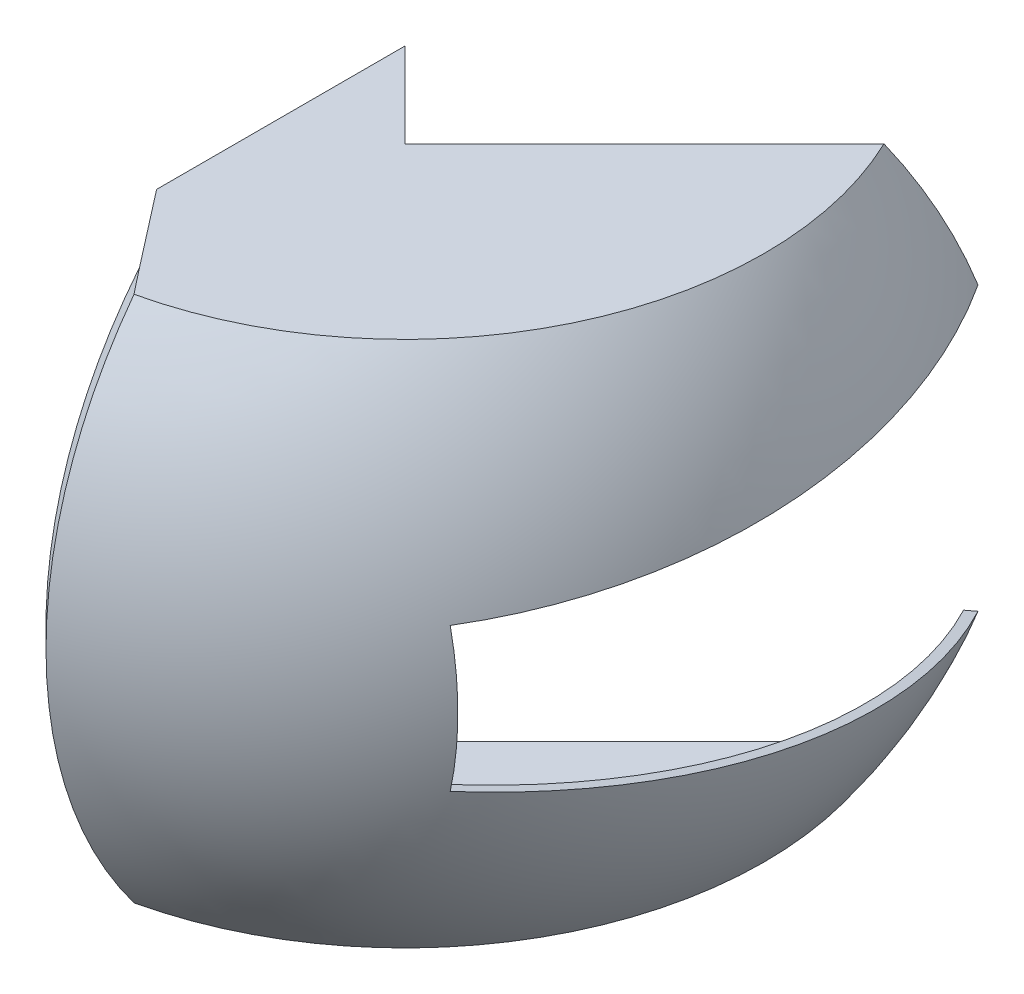
SolidWorks part; units mm, degrees
ref_plane "Płaszczyzna przednia" through (0, 0, 0) normal (0, 0, 1) x (1, 0, 0)
ref_plane "Płaszczyzna górna" through (0, 0, 0) normal (0, 1, 0) x (1, 0, 0)
ref_plane "Płaszczyzna prawa" through (0, 0, 0) normal (1, 0, 0) x (0, 0, -1)
sketch "Szkic1" plane through (0, 0, 0) normal (1, 0, 0) x (0, 0, -1)
  line L0 (0, 0) -> (-111.097, 0) construction
  line L1 (0, -55) -> (0, 55)
  line L2 (0, 55) -> (-75, 55)
  line L3 (0, -55) -> (-75, -55)
  arc A0 (-75, 55) -> (-75, -55) centre (0, 0) ccw
  dimension "D1" = 55
  dimension "D2" = 75
revolve "Obrót1" add sketch "Szkic1" angle 180 about L1
sketch "Szkic2" plane through (0, -55, 0) normal (0, -1, 0) x (1, 0, 0)
  line L0 (0, 0) -> (0, 40)
  line L1 (0, 75) -> (0, -75) construction
  line L2 (0, 40) -> (12.2873, 48.6036)
  line L3 (12.2873, 48.6036) -> (12.2873, 99.4877)
  line L4 (0, 0) -> (17.6777, 17.6777)
  line L5 (17.6777, 17.6777) -> (87.3537, -51.9984)
  line L6 (12.2873, 99.4877) -> (-26.0659, 99.4877)
  line L7 (-26.0659, 99.4877) -> (-26.0659, -104.7585)
  line L8 (-26.0659, -104.7585) -> (87.3537, -104.7585)
  line L9 (87.3537, -104.7585) -> (87.3537, -51.9984)
  dimension "D1" = 40
  dimension "D2" = 125
  dimension "D3" = 15
  dimension "D4" = 25
  dimension "D5" = 45
extrude "Wytnij-wyciągnięcie1" cut sketch "Szkic2" against normal through all
ref_plane "Płaszczyzna1" through (100, 0, 0) normal (1, 0, 0) x (0, 0, -1)
sketch "Szkic3" plane through (100, 0, 0) normal (1, 0, 0) x (0, 0, -1)
  line L1 (-60, -15) -> (-60, 15)
  line L3 (45.6666, -30) -> (45.6666, 30)
  line L4 (45.6666, 30) -> (-60, 15)
  line L5 (45.6666, -30) -> (-60, -15)
extrude "Wytnij-wyciągnięcie2" cut sketch "Szkic3" against normal through all
chamfer "Sfazowanie1" distance 5 angle 45 1 edges at (12.2873, 0, 92.1901)
shell "Skorupa1" thickness 2
sketch "Szkic4" plane through (0, -55, 0) normal (0, -1, 0) x (1, 0, 0)
  line L0 (0, 40) -> (0, 51.8191)
  line L1 (12.2873, 67.6544) -> (0, 51.8191)
  line L2 (0, 40) -> (12.2873, 48.6036)
  line L3 (12.2873, 48.6036) -> (12.2873, 67.6544)
extrude "Dodanie-wyciągnięcie1" add sketch "Szkic4" against normal blind 2
mirror "Lustro1" about plane through (0, 0, 0) normal (0, 1, 0) of "Dodanie-wyciągnięcie1"
